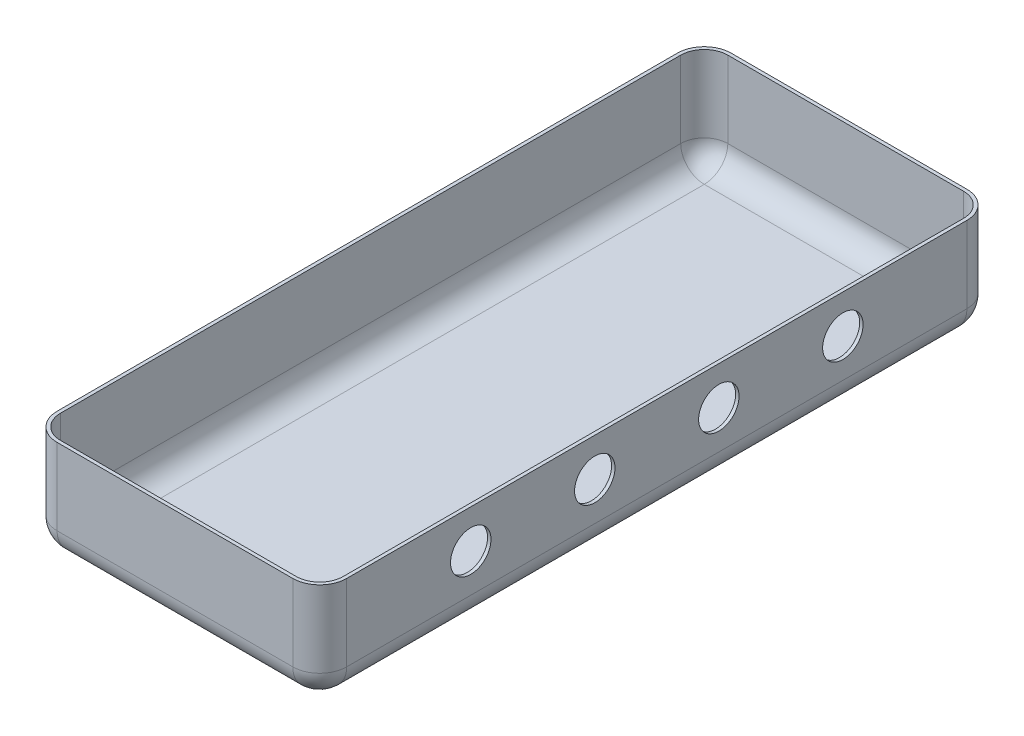
SolidWorks part; units mm, degrees
material "McMaster 6061-T6"
ref_plane "Front" through (0, 0, 0) normal (0, 0, 1) x (1, 0, 0)
ref_plane "Top" through (0, 0, 0) normal (0, 1, 0) x (1, 0, 0)
ref_plane "Right" through (0, 0, 0) normal (1, 0, 0) x (0, 0, -1)
sketch "Sketch1" plane through (0, 0, 0) normal (0, 1, 0) x (1, 0, 0)
  line L1 (0, 0) -> (136.398, 0)
  line L2 (0, 0) -> (0, 317.5)
  line L3 (0, 317.5) -> (136.398, 317.5)
  line L4 (136.398, 0) -> (136.398, 317.5)
  dimension "D1" = 136.398
  dimension "D2" = 317.5
extrude "Boss-Extrude1" add sketch "Sketch1" along normal offset from surface (48.768 mm away) 6.35 offset beyond the face yes
fillet "Fillet1" radius 12.7 8 edges at (0, 0, -158.75) (0, 24.384, -317.5) (68.199, 0, -317.5) (136.398, 24.384, -317.5) (68.199, 0, 0) (136.398, 0, -158.75) (136.398, 24.384, 0) (0, 24.384, 0)
shell "Shell1" thickness 1.6002 removed face at (68.199, 48.768, -158.75)
sketch "Sketch2" plane through (136.398, 0, 0) normal (1, 0, 0) x (0, 0, -1)
  line L0 (12.7, 30.734) -> (71.12, 30.734) construction
  line L1 (12.7, 48.768) -> (12.7, 12.7) construction
  line L2 (71.12, 30.734) -> (129.54, 30.734) construction
  line L3 (129.54, 30.734) -> (187.96, 30.734) construction
  line L4 (187.96, 30.734) -> (246.38, 30.734) construction
  line L5 (246.38, 30.734) -> (304.8, 30.734) construction
  line L6 (304.8, 12.7) -> (304.8, 48.768) construction
  circle A0 centre (71.12, 30.734) radius 9.525
  circle A1 centre (129.54, 30.734) radius 9.525
  circle A2 centre (187.96, 30.734) radius 9.525
  circle A3 centre (246.38, 30.734) radius 9.525
  dimension "D1" = 19.05
extrude "Cut-Extrude1" cut sketch "Sketch2" against normal up to next
